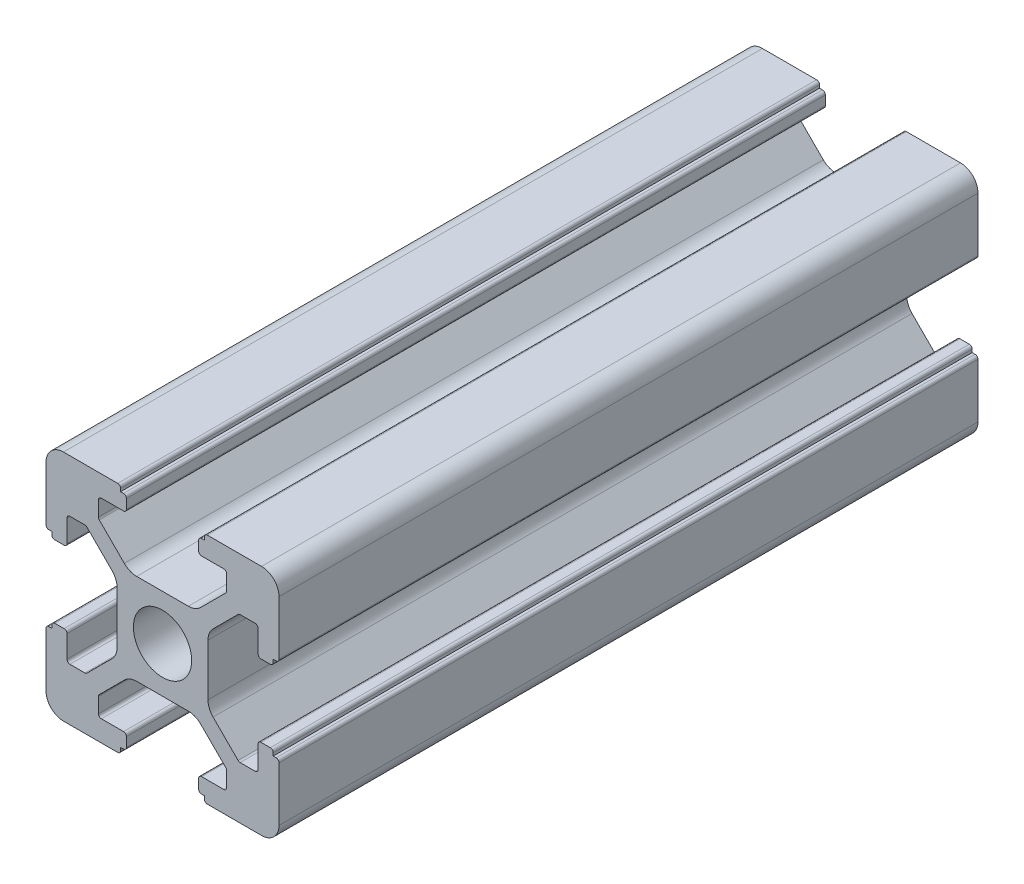
SolidWorks part; units mm, degrees
ref_plane "前视基准面" through (0, 0, 0) normal (0, 0, 1) x (1, 0, 0)
ref_plane "上视基准面" through (0, 0, 0) normal (0, 1, 0) x (1, 0, 0)
ref_plane "右视基准面" through (0, 0, 0) normal (1, 0, 0) x (0, 0, -1)
sketch "草图1" plane through (0, 0, 0) normal (0, 0, 1) x (1, 0, 0)
  line L0 (0, 0) -> (0, 5.5) construction
  line L1 (-8.5023, -10.0023) -> (-3.85, -10.0023)
  line L2 (-10.0023, -8.5023) -> (-10.0023, -3.85)
  line L3 (-8.5023, 10.0023) -> (-3.85, 10.0023)
  line L4 (10.0023, -8.5023) -> (10.0023, -3.85)
  line L5 (-10.0023, -10.0023) -> (10.0023, 10.0023) construction
  line L6 (-10.0023, 10.0023) -> (10.0023, -10.0023) construction
  line L7 (-2.218, -3.9) -> (2.218, -3.9)
  line L8 (-3.9, -2.218) -> (-3.9, 2.218)
  line L9 (-2.218, 3.9) -> (2.218, 3.9)
  line L10 (3.9, -2.218) -> (3.9, 2.218)
  line L11 (-3.9, -3.9) -> (3.9, 3.9) construction
  line L12 (-3.9, 3.9) -> (3.9, -3.9) construction
  line L13 (-5.25, -8.2) -> (-3.35, -8.2)
  line L14 (-8.2, -5.25) -> (-8.2, -3.35)
  line L15 (-5.25, 8.2) -> (-3.35, 8.2)
  line L16 (8.2, -5.25) -> (8.2, -3.35)
  line L17 (-8.2, -8.2) -> (8.2, 8.2) construction
  line L18 (-8.2, 8.2) -> (8.2, -8.2) construction
  line L19 (-7.95, 5.5) -> (-6.6642, 5.5)
  line L20 (0, 0) -> (5.5, 0) construction
  line L23 (-5.5, 7.95) -> (-5.5, 6.6642)
  line L26 (0, 0) -> (-0.5303, 0.5303)
  line L27 (3.2787, 4.3393) -> (5.4268, 6.4874)
  line L28 (0, 0) -> (0.5303, -0.5303)
  line L29 (5.5, 6.6642) -> (5.5, 7.95)
  line L30 (4.3393, 3.2787) -> (6.4874, 5.4268)
  line L31 (6.6642, 5.5) -> (7.95, 5.5)
  line L32 (4.3393, -3.2787) -> (6.4874, -5.4268)
  line L33 (3.2787, -4.3393) -> (5.4268, -6.4874)
  line L34 (-3.2787, -4.3393) -> (-5.4268, -6.4874)
  line L35 (-4.3393, -3.2787) -> (-6.4874, -5.4268)
  line L36 (-4.3393, 3.2787) -> (-6.4874, 5.4268)
  line L37 (-3.2787, 4.3393) -> (-5.4268, 6.4874)
  line L38 (3.1, -8.45) -> (3.1, -9.2523)
  line L39 (8.45, 3.1) -> (9.2523, 3.1)
  line L40 (-5.5, -6.6642) -> (-5.5, -7.95)
  line L41 (-6.6642, -5.5) -> (-7.95, -5.5)
  line L42 (5.5, -6.6642) -> (5.5, -7.95)
  line L43 (6.6642, -5.5) -> (7.95, -5.5)
  line L44 (9.2523, -3.1) -> (8.45, -3.1)
  line L46 (10.0023, 3.85) -> (10.0023, 8.5023)
  line L47 (8.2, 3.35) -> (8.2, 5.25)
  line L48 (-3.1, -9.2523) -> (-3.1, -8.45)
  line L49 (-8.45, -3.1) -> (-9.2523, -3.1)
  line L50 (-9.2523, 3.1) -> (-8.45, 3.1)
  line L51 (-3.1, 8.45) -> (-3.1, 9.2523)
  line L52 (3.1, 9.2523) -> (3.1, 8.45)
  line L53 (3.85, 10.0023) -> (8.5023, 10.0023)
  line L54 (3.35, 8.2) -> (5.25, 8.2)
  line L55 (-10.0023, 3.85) -> (-10.0023, 8.5023)
  line L56 (-8.2, 3.35) -> (-8.2, 5.25)
  line L57 (3.35, -8.2) -> (5.25, -8.2)
  line L58 (3.85, -10.0023) -> (8.5023, -10.0023)
  line L59 (9.7523, -3.6) -> (9.5023, -3.6)
  line L61 (9.7523, 3.6) -> (9.5023, 3.6)
  line L62 (9.5023, -3.6) -> (9.5023, -3.35)
  line L63 (3.6, -9.7523) -> (3.6, -9.5023)
  line L64 (3.35, -9.5023) -> (3.6, -9.5023)
  line L65 (9.5023, 3.35) -> (9.5023, 3.6)
  line L66 (-3.6, -9.5023) -> (-3.35, -9.5023)
  line L67 (-3.6, -9.7523) -> (-3.6, -9.5023)
  line L68 (-9.7523, -3.6) -> (-9.5023, -3.6)
  line L69 (-9.5023, -3.35) -> (-9.5023, -3.6)
  line L70 (-9.5023, 3.6) -> (-9.5023, 3.35)
  line L71 (-9.7523, 3.6) -> (-9.5023, 3.6)
  line L72 (-3.6, 9.7523) -> (-3.6, 9.5023)
  line L73 (-3.35, 9.5023) -> (-3.6, 9.5023)
  line L74 (3.6, 9.5023) -> (3.35, 9.5023)
  line L75 (3.6, 9.7523) -> (3.6, 9.5023)
  circle A0 centre (0, 0) radius 2.5
  arc A1 (10.0023, 8.5023) -> (8.5023, 10.0023) centre (8.5023, 8.5023) ccw
  arc A2 (8.5023, -10.0023) -> (10.0023, -8.5023) centre (8.5023, -8.5023) ccw
  arc A3 (-10.0023, -8.5023) -> (-8.5023, -10.0023) centre (-8.5023, -8.5023) ccw
  arc A4 (-10.0023, 8.5023) -> (-8.5023, 10.0023) centre (-8.5023, 8.5023) cw
  arc A5 (-9.5023, -3.35) -> (-9.2523, -3.1) centre (-9.2523, -3.35) cw
  arc A6 (-9.7523, -3.6) -> (-10.0023, -3.85) centre (-9.7523, -3.85) ccw
  arc A7 (-8.45, -3.1) -> (-8.2, -3.35) centre (-8.45, -3.35) cw
  arc A8 (-7.95, -5.5) -> (-8.2, -5.25) centre (-7.95, -5.25) cw
  arc A9 (-6.4874, -5.4268) -> (-6.6642, -5.5) centre (-6.6642, -5.25) cw
  arc A10 (-5.4268, -6.4874) -> (-5.5, -6.6642) centre (-5.25, -6.6642) ccw
  arc A11 (-5.5, -7.95) -> (-5.25, -8.2) centre (-5.25, -7.95) ccw
  arc A12 (-3.6, -9.7523) -> (-3.85, -10.0023) centre (-3.85, -9.7523) cw
  arc A13 (-3.35, -9.5023) -> (-3.1, -9.2523) centre (-3.35, -9.2523) ccw
  arc A14 (-3.1, -8.45) -> (-3.35, -8.2) centre (-3.35, -8.45) ccw
  arc A15 (3.1, -8.45) -> (3.35, -8.2) centre (3.35, -8.45) cw
  arc A16 (5.5, -7.95) -> (5.25, -8.2) centre (5.25, -7.95) cw
  arc A17 (5.4268, -6.4874) -> (5.5, -6.6642) centre (5.25, -6.6642) cw
  arc A18 (6.4874, -5.4268) -> (6.6642, -5.5) centre (6.6642, -5.25) ccw
  arc A19 (7.95, -5.5) -> (8.2, -5.25) centre (7.95, -5.25) ccw
  arc A20 (8.45, -3.1) -> (8.2, -3.35) centre (8.45, -3.35) ccw
  arc A21 (9.5023, -3.35) -> (9.2523, -3.1) centre (9.2523, -3.35) ccw
  arc A22 (9.7523, -3.6) -> (10.0023, -3.85) centre (9.7523, -3.85) cw
  arc A23 (3.35, -9.5023) -> (3.1, -9.2523) centre (3.35, -9.2523) cw
  arc A24 (3.6, -9.7523) -> (3.85, -10.0023) centre (3.85, -9.7523) ccw
  arc A25 (7.95, 5.5) -> (8.2, 5.25) centre (7.95, 5.25) cw
  arc A26 (8.2, 3.35) -> (8.45, 3.1) centre (8.45, 3.35) ccw
  arc A27 (9.5023, 3.35) -> (9.2523, 3.1) centre (9.2523, 3.35) cw
  arc A28 (9.7523, 3.6) -> (10.0023, 3.85) centre (9.7523, 3.85) ccw
  arc A29 (6.6642, 5.5) -> (6.4874, 5.4268) centre (6.6642, 5.25) ccw
  arc A30 (5.4268, 6.4874) -> (5.5, 6.6642) centre (5.25, 6.6642) ccw
  arc A31 (5.5, 7.95) -> (5.25, 8.2) centre (5.25, 7.95) ccw
  arc A32 (3.1, 8.45) -> (3.35, 8.2) centre (3.35, 8.45) ccw
  arc A33 (3.6, 9.7523) -> (3.85, 10.0023) centre (3.85, 9.7523) cw
  arc A34 (3.35, 9.5023) -> (3.1, 9.2523) centre (3.35, 9.2523) ccw
  arc A35 (-9.7523, 3.6) -> (-10.0023, 3.85) centre (-9.7523, 3.85) cw
  arc A36 (-9.5023, 3.35) -> (-9.2523, 3.1) centre (-9.2523, 3.35) ccw
  arc A37 (-8.45, 3.1) -> (-8.2, 3.35) centre (-8.45, 3.35) ccw
  arc A38 (-8.2, 5.25) -> (-7.95, 5.5) centre (-7.95, 5.25) cw
  arc A39 (-6.4874, 5.4268) -> (-6.6642, 5.5) centre (-6.6642, 5.25) ccw
  arc A40 (-5.4268, 6.4874) -> (-5.5, 6.6642) centre (-5.25, 6.6642) cw
  arc A41 (-5.5, 7.95) -> (-5.25, 8.2) centre (-5.25, 7.95) cw
  arc A42 (-3.1, 8.45) -> (-3.35, 8.2) centre (-3.35, 8.45) cw
  arc A43 (-3.1, 9.2523) -> (-3.35, 9.5023) centre (-3.35, 9.2523) ccw
  arc A44 (-3.6, 9.7523) -> (-3.85, 10.0023) centre (-3.85, 9.7523) ccw
  arc A45 (-4.3393, 3.2787) -> (-3.9, 2.218) centre (-5.4, 2.218) cw
  arc A46 (-3.2787, 4.3393) -> (-2.218, 3.9) centre (-2.218, 5.4) ccw
  arc A47 (3.2787, 4.3393) -> (2.218, 3.9) centre (2.218, 5.4) cw
  arc A48 (4.3393, 3.2787) -> (3.9, 2.218) centre (5.4, 2.218) ccw
  arc A49 (4.3393, -3.2787) -> (3.9, -2.218) centre (5.4, -2.218) cw
  arc A50 (3.2787, -4.3393) -> (2.218, -3.9) centre (2.218, -5.4) ccw
  arc A51 (-4.3393, -3.2787) -> (-3.9, -2.218) centre (-5.4, -2.218) ccw
  arc A52 (-2.218, -3.9) -> (-3.2787, -4.3393) centre (-2.218, -5.4) ccw
  point P0 (0, 0)
  point P7 (10.0023, 0)
  point P62 (0, 0)
  point P76 (0, 0)
  point P92 (-8.2, -5.5)
  point P99 (0, 0)
  point P106 (-5.5, -8.2)
  point P117 (5.5, -8.2)
  point P124 (8.2, -5.5)
  point P137 (8.2, 5.5)
  point P140 (8.2, 3.1)
  point P147 (6.5607, 5.5)
  point P152 (5.5, 8.2)
  point P167 (-8.2, 5.5)
  point P174 (-5.5, 8.2)
  dimension "D1" = 1.5
  dimension "D5" = 0.25
  dimension "D6" = 1.5
  dimension "D2" = 4
  dimension "D3" = 4
  dimension "D4" = 4
extrude "凸台-拉伸1" add sketch "草图1" along normal blind 60 contours A52 L7 A50 L33 A17 L42 A16 L57 A15 L38 A23 L64 L63 A24 L58 A2 L4 A22 L59 L62 A21 L44 A20 L16 A19 L43 A18 L32 A49 L10 A48 L30 A29 L31 A25 L47 A26 L39 A27 L65 L61 A28 L46 A1 L53 A33 L75 L74 A34 L52 A32 region at (-9.3629, -9.3629, 0)
